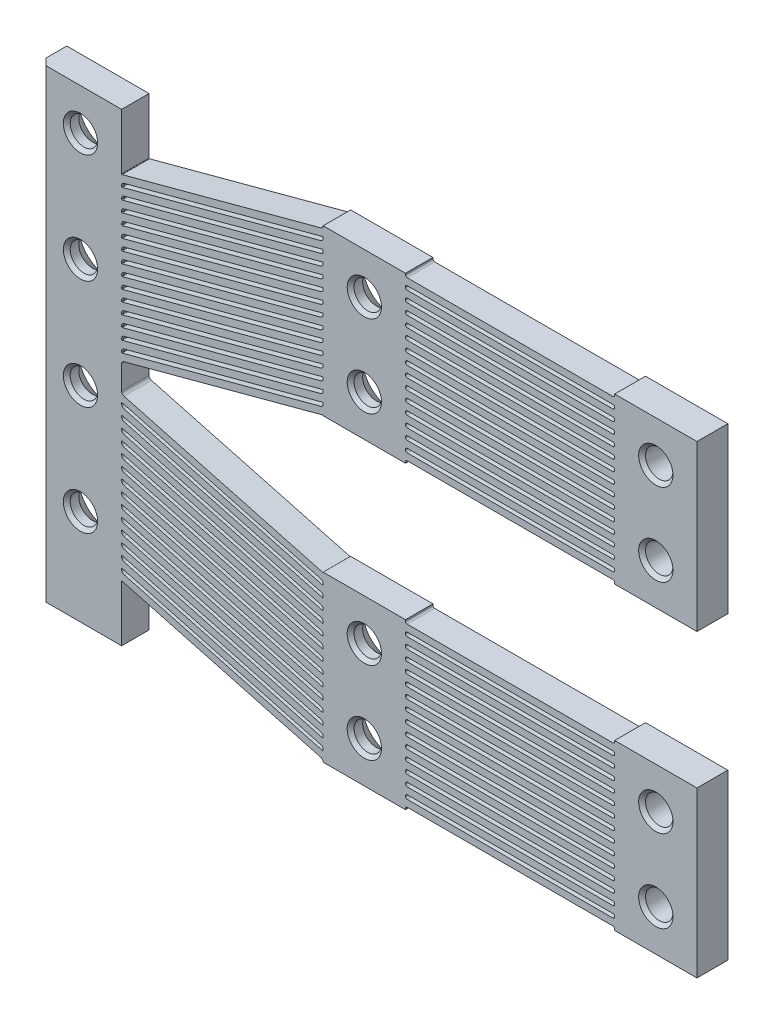
SolidWorks part; units mm, degrees
ref_plane "Front Plane" through (0, 0, 0) normal (0, 0, 1) x (1, 0, 0)
ref_plane "Top Plane" through (0, 0, 0) normal (0, 1, 0) x (1, 0, 0)
ref_plane "Right Plane" through (0, 0, 0) normal (1, 0, 0) x (0, 0, -1)
sketch "Sketch1" plane through (0, 0, 0) normal (0, 0, 1) x (1, 0, 0)
  line L0 (0, 0) -> (9.6, 0)
  line L1 (0, 0) -> (0, 27.1)
  line L11 (76.7152, 19.2) -> (76.7152, 0)
  line L12 (76.7152, 0) -> (67.1152, 0)
  line L14 (66.9152, 0.3519) -> (42.9152, 0.3519)
  line L16 (42.7152, 0) -> (33.1152, 0)
  line L18 (32.8452, 0.3519) -> (9.6629, 6.5635)
  line L21 (9.87, 25.3634) -> (33.0522, 19.1517) construction
  line L28 (0, 27.1) -> (9.6, 27.1)
  line L29 (67.1152, 19.2) -> (76.7152, 19.2)
  line L31 (9.6629, 24.5906) -> (32.8452, 18.379) construction
  line L32 (9.87, 7.3363) -> (33.0522, 1.1246)
  line L34 (9.87, 25.3634) -> (9.6629, 24.5906) construction
  line L35 (9.87, 7.3363) -> (9.6629, 6.5635) construction
  line L36 (9.6, 27.1) -> (9.6, 25.7152)
  line L41 (42.9152, 0.3519) -> (42.9152, 1.1519) construction
  line L44 (42.9152, 18.8481) -> (66.9152, 18.8481) construction
  line L46 (42.9152, 18.0481) -> (66.9152, 18.0481) construction
  line L48 (42.9152, 1.1519) -> (66.9152, 1.1519)
  line L50 (42.9152, 18.0481) -> (42.9152, 18.8481) construction
  line L51 (9.6, 24.5423) -> (9.6, 7.6881)
  line L52 (9.6, 0) -> (9.6, 6.5152)
  line L54 (33.1152, 19.2) -> (42.7152, 19.2)
  line L58 (37.9152, 14.4) -> (37.9152, 4.8) construction
  line L59 (33.1152, 1.1729) -> (33.1152, 18.0271)
  line L60 (33.0522, 1.1246) -> (32.8452, 0.3519) construction
  line L61 (42.7152, 17.8481) -> (42.7152, 1.3519)
  line L62 (67.1152, 1.3519) -> (67.1152, 17.8481)
  line L63 (67.1152, 19.2) -> (67.1152, 19.0481)
  line L64 (42.7152, 0) -> (42.7152, 0.1519)
  line L65 (42.7152, 19.0481) -> (42.7152, 19.2)
  line L66 (67.1152, 0.1519) -> (67.1152, 0)
  line L67 (9.6, 25.7152) -> (9.6, 24.5423)
  line L69 (67.1152, 19.0481) -> (67.1152, 17.8481)
  line L71 (33.1152, 19.2) -> (33.1152, 18.0271)
  line L72 (42.7152, 19.0481) -> (42.7152, 17.8481)
  line L73 (37.9152, 16.6) -> (37.9152, 19.2) construction
  line L74 (37.9152, 0) -> (37.9152, 2.6) construction
  circle A0 centre (4.8, 4.8) radius 4.8 construction
  circle A1 centre (4.8, 4.8) radius 1.6 construction
  circle A6 centre (37.9152, 4.8) radius 4.8 construction
  circle A7 centre (71.9152, 4.8) radius 4.8 construction
  circle A10 centre (71.9152, 4.8) radius 1.6
  circle A11 centre (37.9152, 4.8) radius 1.6
  circle A13 centre (37.9152, 14.4) radius 4.8 construction
  circle A15 centre (37.9152, 14.4) radius 1.6
  arc A24 (9.6, 25.7152) -> (9.87, 25.3634) centre (9.9643, 25.7152) ccw construction
  arc A25 (9.6629, 24.5906) -> (9.6, 24.5423) centre (9.65, 24.5423) ccw construction
  arc A26 (9.6, 7.6881) -> (9.87, 7.3363) centre (9.9643, 7.6881) ccw
  arc A27 (9.6, 6.5152) -> (9.6629, 6.5635) centre (9.65, 6.5152) cw
  arc A28 (32.8452, 0.3519) -> (33.1152, 0) centre (32.7509, 0) cw
  arc A29 (33.0522, 1.1246) -> (33.1152, 1.1729) centre (33.0652, 1.1729) ccw
  arc A30 (33.1152, 18.0271) -> (32.8452, 18.379) centre (32.7509, 18.0271) ccw construction
  arc A31 (33.0522, 19.1517) -> (33.1152, 19.2) centre (33.0652, 19.2) ccw construction
  arc A34 (42.9152, 1.1519) -> (42.7152, 1.3519) centre (42.9152, 1.3519) cw
  arc A35 (42.9152, 18.0481) -> (42.7152, 17.8481) centre (42.9152, 17.8481) ccw construction
  arc A37 (66.9152, 1.1519) -> (67.1152, 1.3519) centre (66.9152, 1.3519) ccw
  arc A38 (66.9152, 18.0481) -> (67.1152, 17.8481) centre (66.9152, 17.8481) cw construction
  arc A39 (67.1152, 19.0481) -> (66.9152, 18.8481) centre (66.9152, 19.0481) cw construction
  arc A40 (42.9152, 0.3519) -> (42.7152, 0.1519) centre (42.9152, 0.1519) ccw
  arc A41 (42.9152, 18.8481) -> (42.7152, 19.0481) centre (42.9152, 19.0481) cw construction
  arc A42 (66.9152, 0.3519) -> (67.1152, 0.1519) centre (66.9152, 0.1519) cw
  circle A43 centre (71.9152, 14.4) radius 4.8 construction
  circle A44 centre (71.9152, 14.4) radius 1.6
  circle A45 centre (37.9152, 16.6) radius 6.5 construction
  circle A46 centre (37.9152, 2.6) radius 6.5 construction
  point P39 (32.9487, 0.7382)
  point P78 (37.9152, 10.1)
  point P79 (37.9152, 9.1)
  point P80 (37.9152, 23.1)
  point P81 (0, 0)
  point P82 (9.6, 30.6235)
  dimension "D1" = 3.2
  dimension "D2" = 3.2
  dimension "D6" = 0.2
  dimension "D8" = 0.05
  dimension "D10" = 13
  dimension "D3" = 15
  dimension "D4" = 0.8
  dimension "D5" = 10.5
  dimension "D7" = 24
  dimension "D9" = 76.7152
  dimension "D11" = 1
extrude "Boss-Extrude1" add sketch "Sketch1" along normal blind 3.2
sketch "Sketch3" plane through (0, 0, 3.2) normal (0, 0, 1) x (1, 0, 0)
  line L0 (33.1152, 19.2) -> (33.1152, 18.0271) construction
  line L1 (9.87, 25.3634) -> (33.0522, 19.1517) construction
  line L2 (9.6629, 24.5906) -> (32.8452, 18.379) construction
  line L3 (9.6, 25.7152) -> (9.6, 24.5423) construction
  line L4 (33.1152, 19.2) -> (33.1152, 18.0271)
  line L5 (9.87, 25.3634) -> (33.0522, 19.1517)
  line L6 (9.6629, 24.5906) -> (32.8452, 18.379)
  line L7 (9.6, 25.7152) -> (9.6, 24.5423)
  arc A0 (33.1152, 18.0271) -> (32.8452, 18.379) centre (32.7509, 18.0271) ccw construction
  arc A1 (33.0522, 19.1517) -> (33.1152, 19.2) centre (33.0652, 19.2) ccw construction
  arc A2 (9.6629, 24.5906) -> (9.6, 24.5423) centre (9.65, 24.5423) ccw construction
  arc A3 (9.6, 25.7152) -> (9.87, 25.3634) centre (9.9643, 25.7152) ccw construction
  arc A4 (33.1152, 18.0271) -> (32.8452, 18.379) centre (32.7509, 18.0271) ccw
  arc A5 (33.0522, 19.1517) -> (33.1152, 19.2) centre (33.0652, 19.2) ccw
  arc A6 (9.6629, 24.5906) -> (9.6, 24.5423) centre (9.65, 24.5423) ccw
  arc A7 (9.6, 25.7152) -> (9.87, 25.3634) centre (9.9643, 25.7152) ccw
extrude "Boss-Extrude3" add sketch "Sketch3" against normal up to surface (3.2 mm away) up to face at (38.3551, 6.2136, 0)
pattern_linear "LPattern2" count 15 spacing 1.2876 along (0, -1, 0) of "Boss-Extrude3"
sketch "Sketch4" plane through (0, 0, 3.2) normal (0, 0, 1) x (1, 0, 0)
  line L0 (67.1152, 19.0481) -> (67.1152, 17.8481) construction
  line L1 (42.9152, 18.8481) -> (66.9152, 18.8481) construction
  line L2 (42.9152, 18.0481) -> (66.9152, 18.0481) construction
  line L3 (42.7152, 19.0481) -> (42.7152, 17.8481) construction
  line L4 (67.1152, 19.0481) -> (67.1152, 17.8481)
  line L5 (42.9152, 18.8481) -> (66.9152, 18.8481)
  line L6 (42.9152, 18.0481) -> (66.9152, 18.0481)
  line L7 (42.7152, 19.0481) -> (42.7152, 17.8481)
  arc A0 (66.9152, 18.8481) -> (67.1152, 19.0481) centre (66.9152, 19.0481) ccw construction
  arc A1 (67.1152, 17.8481) -> (66.9152, 18.0481) centre (66.9152, 17.8481) ccw construction
  arc A2 (42.9152, 18.0481) -> (42.7152, 17.8481) centre (42.9152, 17.8481) ccw construction
  arc A3 (42.7152, 19.0481) -> (42.9152, 18.8481) centre (42.9152, 19.0481) ccw construction
  arc A4 (66.9152, 18.8481) -> (67.1152, 19.0481) centre (66.9152, 19.0481) ccw
  arc A5 (67.1152, 17.8481) -> (66.9152, 18.0481) centre (66.9152, 17.8481) ccw
  arc A6 (42.9152, 18.0481) -> (42.7152, 17.8481) centre (42.9152, 17.8481) ccw
  arc A7 (42.7152, 19.0481) -> (42.9152, 18.8481) centre (42.9152, 19.0481) ccw
extrude "Boss-Extrude4" add sketch "Sketch4" against normal up to surface (3.2 mm away) up to face at (21.3576, 4.4879, 0)
pattern_linear "LPattern3" count 15 spacing 1.264 along (0, -1, 0) of "Boss-Extrude4"
sketch "Sketch5" plane through (0, 0, 0) normal (0, 0, -1) x (-1, 0, 0)
  line L1 (-76.7152, 19.2) -> (-67.1152, 19.2)
  line L2 (-76.7152, 19.2) -> (-76.7152, 0)
  line L3 (-76.7152, 0) -> (-67.1152, 0)
  line L4 (-67.1152, 19.2) -> (-67.1152, 0)
  circle A0 centre (-71.9152, 4.8) radius 1.6 construction
  circle A1 centre (-71.9152, 14.4) radius 1.6 construction
  circle A2 centre (-71.9152, 4.8) radius 1.6
  circle A3 centre (-71.9152, 14.4) radius 1.6
extrude "Boss-Extrude5" add sketch "Sketch5" along normal blind 0.4
chamfer "Chamfer1" distance 0.8 angle 45 1 edges at (0, 13.55, 3.2)
mirror "Mirror1" about plane through (0, 27.1, 3.2) normal (0, -1, 0) of bodies 109 107
sketch "Sketch6" plane through (0, 0, 0) normal (0, 0, -1) x (-1, 0, 0)
  line L0 (0, 54.2) -> (0, 0) construction
  line L1 (0, 54.2) -> (-9.6, 54.2) construction
  line L2 (-9.6, 54.2) -> (-9.6, 47.6848) construction
  line L3 (-4.8, 17.5429) -> (-4.8, 11.1714) construction
  line L4 (-4.8, 17.5429) -> (-4.8, 23.9143) construction
  line L5 (-4.8, 23.9143) -> (-4.8, 30.2857) construction
  line L6 (-4.8, 30.2857) -> (-4.8, 36.6571) construction
  line L7 (-4.8, 36.6571) -> (-4.8, 43.0286) construction
  line L8 (-4.8, 43.0286) -> (-4.8, 49.4) construction
  line L9 (-4.8, 11.1714) -> (-4.8, 4.8) construction
  circle A0 centre (-4.8, 49.4) radius 4.8 construction
  circle A1 centre (-4.8, 4.8) radius 4.8 construction
  circle A2 centre (-4.8, 4.8) radius 4.8 construction
  circle A3 centre (-4.8, 4.8) radius 1.6 construction
  circle A4 centre (-4.8, 4.8) radius 1.6 construction
  circle A5 centre (-4.8, 23.9143) radius 1.6
  circle A6 centre (-4.8, 36.6571) radius 1.6
  circle A7 centre (-4.8, 49.4) radius 1.6
  circle A8 centre (-4.8, 11.1714) radius 1.6
extrude "Cut-Extrude1" cut sketch "Sketch6" against normal through all
chamfer "Chamfer3" distance 1.8 angle 45 8 edges at (39.5152, 14.4, 0) (39.5152, 4.8, 0) (39.5152, 49.4, 0) (39.5152, 39.8, 0) (3.2, 49.4, 0) (3.2, 36.6571, 0) (3.2, 23.9143, 0) (3.2, 11.1714, 0)
chamfer "Chamfer2" distance 0.4 angle 45 16 edges at (73.5152, 4.8, 3.2) (39.5152, 14.4, 3.2) (39.5152, 4.8, 3.2) (73.5152, 14.4, 3.2) (70.3152, 4.8, -0.4) (70.3152, 14.4, -0.4) (3.2, 23.9143, 3.2) (3.2, 36.6571, 3.2) (3.2, 49.4, 3.2) (70.3152, 39.8, -0.4) (73.5152, 39.8, 3.2) (70.3152, 49.4, -0.4) (73.5152, 49.4, 3.2) (39.5152, 49.4, 3.2) (39.5152, 39.8, 3.2) (3.2, 11.1714, 3.2)
